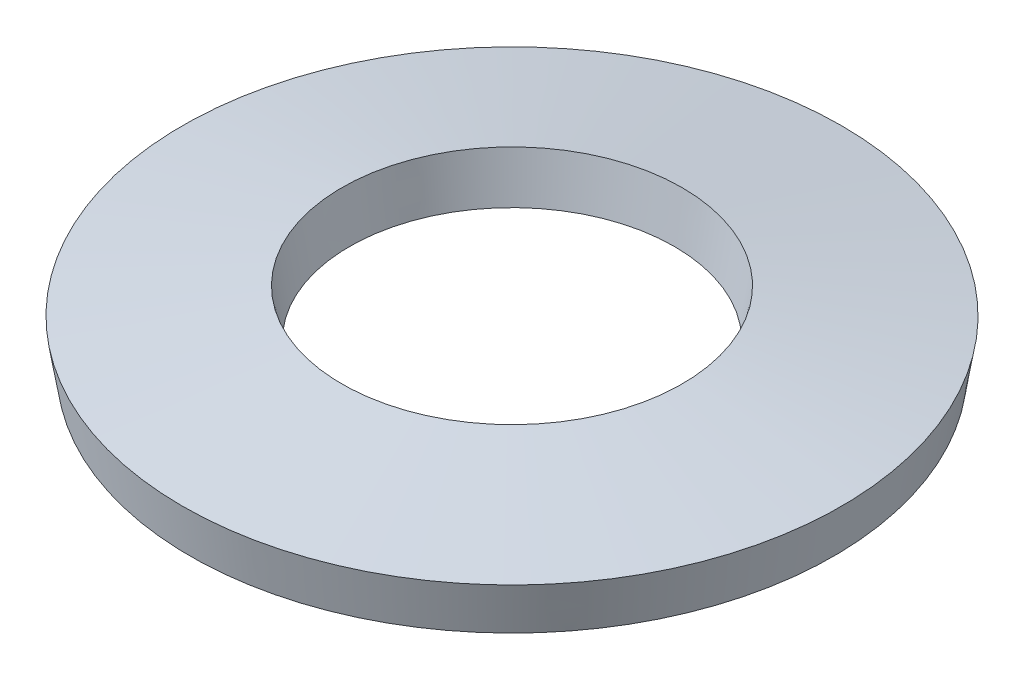
SolidWorks part; units mm, degrees
ref_plane "Front" through (0, 0, 0) normal (0, 0, 1) x (1, 0, 0)
ref_plane "Top" through (0, 0, 0) normal (0, 1, 0) x (1, 0, 0)
ref_plane "Right" through (0, 0, 0) normal (1, 0, 0) x (0, 0, -1)
sketch "Sketch1" plane through (0, 0, 0) normal (0, 0, 1) x (1, 0, 0)
  line L0 (10.1077, 0) -> (5.1, 0.8197)
  line L1 (5.1, 0.8197) -> (5.3423, 2.3)
  line L2 (5.3423, 2.3) -> (10.35, 1.4803)
  line L3 (10.35, 1.4803) -> (10.1077, 0)
  line L4 (0, 0) -> (0, 2.3) construction
  line L5 (-10.35, 1.4803) -> (-10.1077, 0) construction
  line L6 (-5.3423, 2.3) -> (-10.35, 1.4803) construction
  line L7 (-5.1, 0.8197) -> (-5.3423, 2.3) construction
  line L8 (-10.1077, 0) -> (-5.1, 0.8197) construction
  point P5 (5.2212, 1.5599)
  point P8 (-5.2212, 1.5599)
  dimension "D1" = 5.0743
  dimension "ID" = 10.2
  dimension "OD" = 20.7
  dimension "Thickness" = 1.5
  dimension "Height" = 2.3
revolve "Revolve1" add sketch "Sketch1" angle 360 about L4
sketch "Sketch15" plane through (0, 0, 0) normal (0, 1, 0) x (1, 0, 0)
  circle A0 centre (0, 0) radius 10.35
  circle A1 centre (0, 0) radius 5.1
ref_plane "Contact Plane 1" through (0, 0, 0) normal (0, 1, 0) x (-1, 0, 0)
ref_plane "Contact Plane 2" through (0, 2.3, 0) normal (0, 1, 0) x (-1, 0, 0)
ref_axis "Center Axis 1" through (0, 0, 0) along (0, 1, 0)
